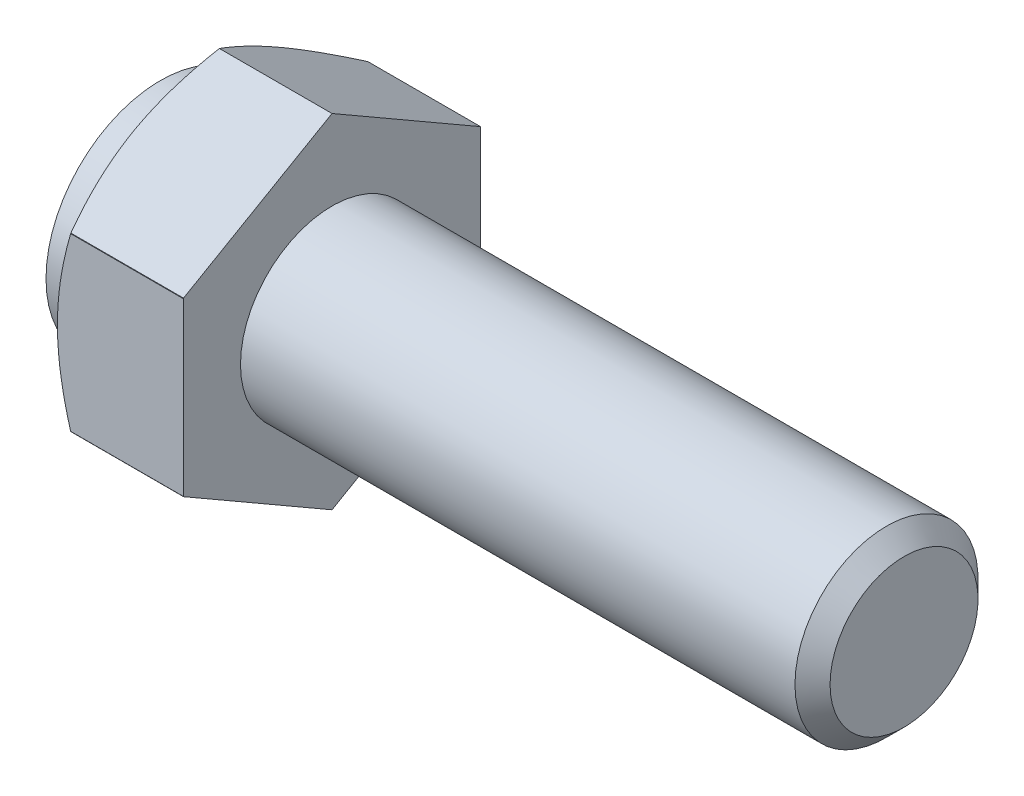
SolidWorks part; units mm, degrees
ref_plane "前视基准面" through (0, 0, 0) normal (0, 0, 1) x (1, 0, 0)
ref_plane "上视基准面" through (0, 0, 0) normal (0, 1, 0) x (1, 0, 0)
ref_plane "右视基准面" through (0, 0, 0) normal (1, 0, 0) x (0, 0, -1)
sketch "草图1" plane through (0, 0, 0) normal (0, 0, 1) x (1, 0, 0)
  line L0 (-7.5, 0) -> (-7.5, 5)
  line L1 (-7.5, 5) -> (-5.5, 5)
  line L2 (-5.5, 5) -> (-5.5, 6.5)
  line L3 (-5.5, 6.5) -> (-4.9226, 7.5)
  line L4 (-4.9226, 7.5) -> (0, 7.5)
  line L5 (0, 7.5) -> (0, 4)
  line L6 (0, 4) -> (24.233, 4)
  line L7 (24.233, 4) -> (25, 3.233)
  line L8 (25, 3.233) -> (25, 0)
  line L9 (25, 0) -> (-7.5, 0)
  line L10 (25, 0) -> (-7.5, 0) construction
revolve "旋转1" add sketch "草图1" angle 360 about L10 reverse direction yes
cosmetic thread "装饰螺纹线1" parameters "D1"=22.5, "D2"=6.466
ref_plane "基准面1" through (12.5, 0, 0) normal (1, 0, 0) x (0, 0, -1)
ref_plane "基准面2" through (25, 0, 0) normal (1, 0, 0) x (0, 0, -1)
sketch "草图2" plane through (0, 0, 0) normal (1, 0, 0) x (0, 0, -1)
  line L0 (-15, -15) -> (15, -15)
  line L1 (15, -15) -> (15, 15)
  line L2 (15, 15) -> (-15, 15)
  line L3 (-15, 15) -> (-15, -15)
  line L4 (-6.5, 3.7528) -> (-6.5, -3.7528)
  line L5 (-6.5, -3.7528) -> (0, -7.5)
  line L6 (0, -7.5) -> (6.5, -3.7528)
  line L7 (6.5, -3.7528) -> (6.5, 3.7528)
  line L8 (6.5, 3.7528) -> (0, 7.5)
  line L9 (0, 7.5) -> (-6.5, 3.7528)
extrude "切除-拉伸1" cut sketch "草图2" against normal blind 7.5
ref_plane "ustb_n XY" through (12.5, 0, 0) normal (1, 0, 0) x (0, 0, -1)
ref_plane "ustb_n XZ" through (0, 0, 0) normal (0, -1, 0) x (1, 0, 0)
ref_plane "ustb_n YZ" through (0, 0, 0) normal (0, 0, -1) x (-1, 0, 0)
ref_axis "ustb_n X" through (12.5, 0, 80.9) along (0, 0, -1)
ref_axis "ustb_n Y" through (12.5, -50, 0) along (0, 1, 0)
ref_axis "ustb_n Z" through (80.9, 0, 0) along (-1, 0, 0)
sketch3d "ustb_n"
  point P0 (12.5, 0, 0)
